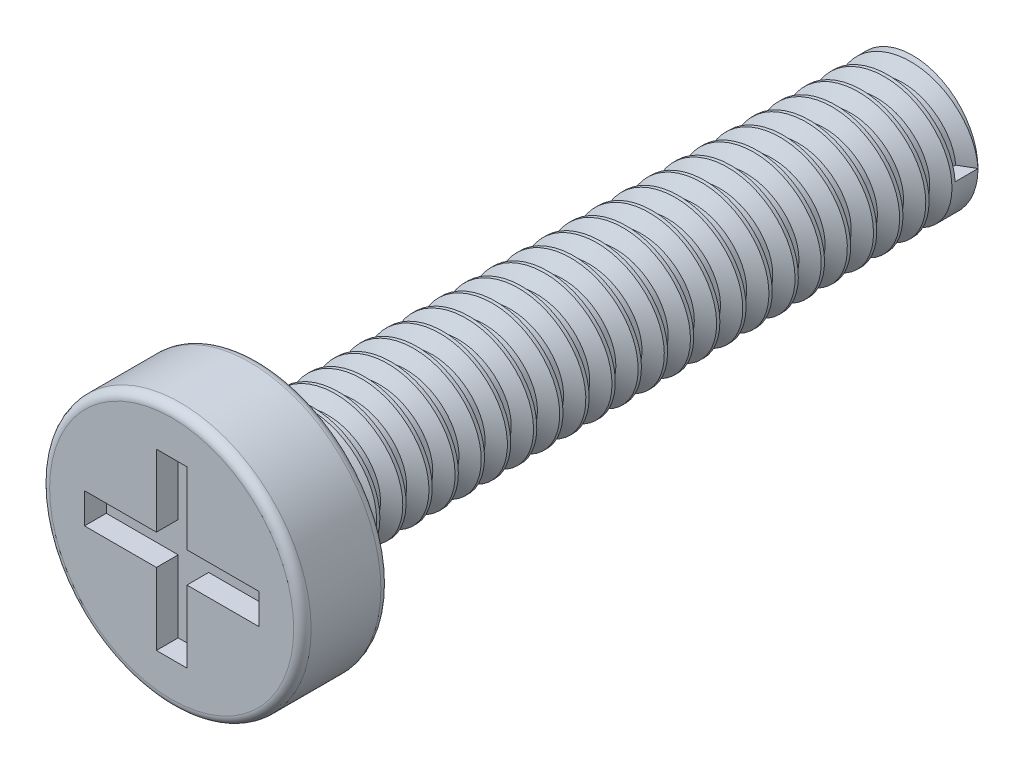
SolidWorks part; units mm, degrees
ref_plane "Front Plane" through (0, 0, 0) normal (0, 0, 1) x (1, 0, 0)
ref_plane "Top Plane" through (0, 0, 0) normal (0, 1, 0) x (1, 0, 0)
ref_plane "Right Plane" through (0, 0, 0) normal (1, 0, 0) x (0, 0, -1)
sketch "Sketch1" plane through (0, 0, 0) normal (0, 0, 1) x (1, 0, 0)
  circle A0 centre (0, 0) radius 1.5
  dimension "D1" = 3
extrude "Boss-Extrude1" add sketch "Sketch1" along normal blind 15
sketch "Sketch2" plane through (0, 0, 15) normal (0, 0, 1) x (1, 0, 0)
  circle A0 centre (0, 0) radius 3
  dimension "D1" = 6
extrude "Boss-Extrude2" add sketch "Sketch2" along normal blind 2
sketch "Sketch7" plane through (0, 0, 17) normal (0, 0, 1) x (1, 0, 0)
  line L1 (0.35, 2) -> (-0.35, 2)
  line L2 (0.35, 2) -> (0.35, -2)
  line L3 (0.35, -2) -> (-0.35, -2)
  line L4 (-0.35, 2) -> (-0.35, -2)
  line L5 (0, -2) -> (0, 2) construction
  line L6 (0.35, 0) -> (-0.35, 0) construction
  line L7 (2, -0.35) -> (-2, -0.35)
  line L8 (2, -0.35) -> (2, 0.35)
  line L9 (2, 0.35) -> (-2, 0.35)
  line L10 (-2, -0.35) -> (-2, 0.35)
  line L11 (0, 0.35) -> (0, -0.35) construction
  line L12 (2, 0) -> (-2, 0) construction
  point P0 (0, 0)
  point P4 (0, 0)
  dimension "D1" = 4
  dimension "D2" = 0.7
extrude "Cut-Extrude1" cut sketch "Sketch7" against normal blind 0.5 contours L9 L2 L1 L4 | L8 L9 L2 L7 | L2 L7 L4 L3 | L10 L7 L4 L9 | L2 L9 L4 L7 region at (0, 1.175, 17) region at (1.175, 0, 17) region at (0, 0, 17) region at (-1.175, 0, 17) region at (0, -1.175, 17)
fillet "Fillet1" radius 0.2 2 edges at (3, 0, 17) (3, 0, 15)
thread "Thread1" pitch 0.6 method cut profile "Thread Profile1" start angle 0, offset 0, length 0, pitch 0.6, diameter 3
ref_plane "Plane1" through (1.5, 0, 0) normal (0, -1, 0) x (1, 0, 0)
sketch "Thread Profile1" plane through (1.5, 0, 0) normal (0, -1, 0) x (1, 0, 0)
  line L0 (0, 0) -> (0, 0.6) construction
  line L11 (0, 0) -> (0, 0.525)
  line L12 (0, 0.525) -> (-0.3248, 0.3375)
  line L13 (-0.3248, 0.3375) -> (-0.3248, 0.1875)
  line L15 (-0.3248, 0.1875) -> (0, 0)
  line L17 (-0.3248, 0.2625) -> (0, 0.2625) construction
  point P2 (0, 0)
  dimension "Pitch" = 0.6
  dimension "Profile_Angle" = 60
  dimension "Profile_Land" = 0.15
  dimension "Profile_Height" = 0.3248
